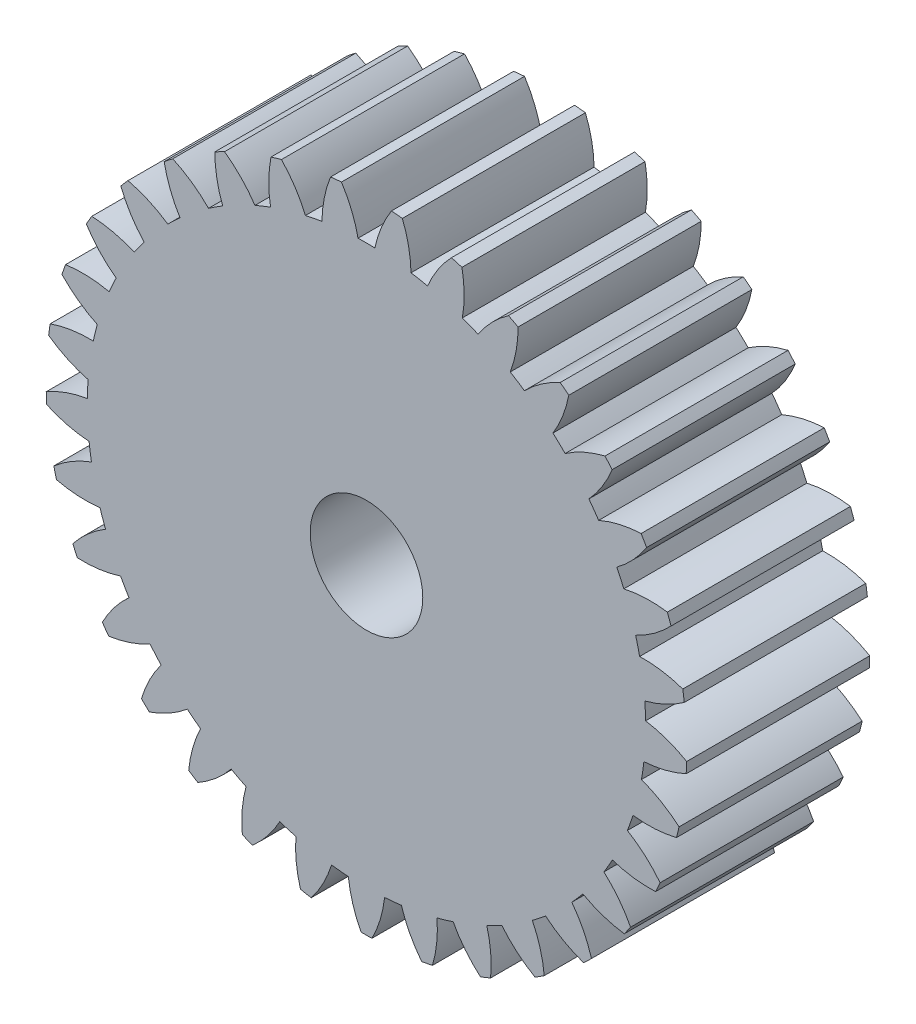
SolidWorks part; units mm, degrees
ref_plane "Alzado" through (0, 0, 0) normal (0, 0, 1) x (1, 0, 0)
ref_plane "Planta" through (0, 0, 0) normal (0, 1, 0) x (1, 0, 0)
ref_plane "Vista lateral" through (0, 0, 0) normal (1, 0, 0) x (0, 0, -1)
sketch "Croquis1" plane through (0, 0, 0) normal (0, 0, 1) x (1, 0, 0)
  line L0 (13.6206, 0) -> (-13.971, 0) construction
  line L1 (-0.46, 15.2421) -> (0, 0) construction
  line L2 (0.46, 15.2421) -> (0, 0) construction
  line L3 (1.3662, 17.4466) -> (0, 0) construction
  line L4 (1.9603, 17.3899) -> (0, 0) construction
  line L5 (0, -3.6901) -> (0, 21.5552) construction
  circle A0 centre (0, 0) radius 3.075
  arc A29 (2.4329, 15.0537) -> (1.9603, 17.3899) centre (-4.1661, 14.9347) ccw
  arc A30 (1.9603, 17.3899) -> (1.3662, 17.4466) centre (0, 0) ccw
  arc A31 (1.3662, 17.4466) -> (0.46, 15.2421) centre (6.9172, 13.8764) ccw
  arc A32 (0.46, 15.2421) -> (-0.46, 15.2421) centre (0, 0) ccw
  circle A133 centre (0, 0) radius 15.249 construction
  circle A134 centre (0, 0) radius 17.5 construction
  arc A135 (3.3363, 14.8796) -> (2.4329, 15.0537) centre (0, 0) ccw
  arc A136 (4.6433, 16.8728) -> (3.3363, 14.8796) centre (9.4183, 12.3166) ccw
  arc A137 (5.2159, 16.7046) -> (4.6433, 16.8728) centre (0, 0) ccw
  arc A138 (5.2378, 14.3212) -> (5.2159, 16.7046) centre (-1.2644, 15.4533) ccw
  arc A139 (6.092, 13.9793) -> (5.2378, 14.3212) centre (0, 0) ccw
  arc A140 (7.7526, 15.6891) -> (6.092, 13.9793) centre (11.5791, 10.3116) ccw
  arc A141 (8.283, 15.4156) -> (7.7526, 15.6891) centre (0, 0) ccw
  arc A142 (7.8535, 13.0712) -> (8.283, 15.4156) centre (1.683, 15.4133) ccw
  arc A143 (8.6275, 12.5737) -> (7.8535, 13.0712) centre (0, 0) ccw
  arc A144 (10.5816, 13.9384) -> (8.6275, 12.5737) centre (13.3213, 7.9339) ccw
  arc A145 (11.0508, 13.5695) -> (10.5816, 13.9384) centre (0, 0) ccw
  arc A146 (10.1853, 11.3487) -> (11.0508, 13.5695) centre (4.5696, 14.8163) ccw
  arc A147 (10.8512, 10.7137) -> (10.1853, 11.3487) centre (0, 0) ccw
  arc A148 (13.0283, 11.6839) -> (10.8512, 10.7137) centre (14.582, 5.2694) ccw
  arc A149 (13.4191, 11.2329) -> (13.0283, 11.6839) centre (0, 0) ccw
  arc A150 (12.149, 9.216) -> (13.4191, 11.2329) centre (7.291, 13.6837) ccw
  arc A151 (12.6827, 8.4665) -> (12.149, 9.216) centre (0, 0) ccw
  arc A152 (15.004, 9.0072) -> (12.6827, 8.4665) centre (15.3158, 2.4145) ccw
  arc A153 (15.3024, 8.4903) -> (15.004, 9.0072) centre (0, 0) ccw
  arc A154 (13.6736, 6.7502) -> (15.3024, 8.4903) centre (9.7489, 12.0566) ccw
  arc A155 (14.0558, 5.9133) -> (13.6736, 6.7502) centre (0, 0) ccw
  arc A156 (16.4375, 6.0049) -> (14.0558, 5.9133) centre (15.4959, -0.5276) ccw
  arc A157 (16.6327, 5.4409) -> (16.4375, 6.0049) centre (0, 0) ccw
  arc A158 (14.704, 4.0405) -> (16.6327, 5.4409) centre (11.8545, 9.9937) ccw
  arc A159 (14.9209, 3.1464) -> (14.704, 4.0405) centre (0, 0) ccw
  arc A160 (17.2769, 2.7855) -> (14.9209, 3.1464) centre (15.1161, -3.4507) ccw
  arc A161 (17.3618, 2.1948) -> (17.2769, 2.7855) centre (0, 0) ccw
  arc A162 (15.2029, 1.1848) -> (17.3618, 2.1948) centre (13.5316, 7.5696) ccw
  arc A163 (15.2467, 0.2657) -> (15.2029, 1.1848) centre (0, 0) ccw
  arc A164 (17.4918, -0.5345) -> (15.2467, 0.2657) centre (14.1898, -6.2491) ccw
  arc A165 (17.4634, -1.1306) -> (17.4918, -0.5345) centre (0, 0) ccw
  arc A166 (15.1524, -1.7138) -> (17.4634, -1.1306) centre (14.7196, 4.872) ccw
  arc A167 (15.0214, -2.6245) -> (15.1524, -1.7138) centre (0, 0) ccw
  arc A168 (17.0746, -3.8352) -> (15.0214, -2.6245) centre (12.7508, -8.8216) ccw
  arc A169 (16.9339, -4.4152) -> (17.0746, -3.8352) centre (0, 0) ccw
  arc A170 (14.5542, -4.5505) -> (16.9339, -4.4152) centre (15.3756, 1.9982) ccw
  arc A171 (14.2533, -5.4199) -> (14.5542, -4.5505) centre (0, 0) ccw
  arc A172 (16.0402, -6.9973) -> (14.2533, -5.4199) centre (10.8508, -11.0753) ccw
  arc A173 (15.7923, -7.5401) -> (16.0402, -6.9973) centre (0, 0) ccw
  arc A174 (13.43, -7.2226) -> (15.7923, -7.5401) centre (15.4759, -0.9477) ccw
  arc A175 (12.97, -8.0194) -> (13.43, -7.2226) centre (0, 0) ccw
  arc A176 (14.4261, -9.9064) -> (12.97, -8.0194) centre (8.5587, -12.9287) ccw
  arc A177 (14.0799, -10.3926) -> (14.4261, -9.9064) centre (0, 0) ccw
  arc A178 (11.8204, -9.6338) -> (14.0799, -10.3926) centre (15.0169, -3.8594) ccw
  arc A179 (11.2179, -10.3291) -> (11.8204, -9.6338) centre (0, 0) ccw
  arc A180 (12.2906, -12.4576) -> (11.2179, -10.3291) centre (5.9573, -14.3148) ccw
  arc A181 (11.8587, -12.8694) -> (12.2906, -12.4576) centre (0, 0) ccw
  arc A182 (9.7836, -11.6967) -> (11.8587, -12.8694) centre (14.0151, -6.6317) ccw
  arc A183 (9.0604, -12.2654) -> (9.7836, -11.6967) centre (0, 0) ccw
  arc A184 (9.7109, -14.5585) -> (9.0604, -12.2654) centre (3.1405, -15.1835) ccw
  arc A185 (9.2088, -14.8811) -> (9.7109, -14.5585) centre (0, 0) ccw
  arc A186 (7.3932, -13.3369) -> (9.2088, -14.8811) centre (12.5068, -9.1642) ccw
  arc A187 (6.5754, -13.7585) -> (7.3932, -13.3369) centre (0, 0) ccw
  arc A188 (6.7802, -16.1332) -> (6.5754, -13.7585) centre (0.2103, -15.5035) ccw
  arc A189 (6.2261, -16.355) -> (6.7802, -16.1332) centre (0, 0) ccw
  arc A190 (4.7356, -14.495) -> (6.2261, -16.355) centre (10.5465, -11.3655) ccw
  arc A191 (3.8528, -14.7543) -> (4.7356, -14.495) centre (0, 0) ccw
  arc A192 (3.6044, -17.1248) -> (3.8528, -14.7543) centre (-2.7276, -15.2631) ccw
  arc A193 (3.0184, -17.2377) -> (3.6044, -17.1248) centre (0, 0) ccw
  arc A194 (1.9068, -15.1293) -> (3.0184, -17.2377) centre (8.2049, -13.1561) ccw
  arc A195 (0.9909, -15.2168) -> (1.9068, -15.1293) centre (0, 0) ccw
  arc A196 (0.2984, -17.4975) -> (0.9909, -15.2168) centre (-5.5668, -14.4711) ccw
  arc A197 (-0.2984, -17.4975) -> (0.2984, -17.4975) centre (0, 0) ccw
  arc A198 (-0.9909, -15.2168) -> (-0.2984, -17.4975) centre (5.5668, -14.4711) ccw
  arc A199 (-1.9068, -15.1293) -> (-0.9909, -15.2168) centre (0, 0) ccw
  arc A200 (-3.0184, -17.2377) -> (-1.9068, -15.1293) centre (-8.2049, -13.1561) ccw
  arc A201 (-3.6044, -17.1248) -> (-3.0184, -17.2377) centre (0, 0) ccw
  arc A202 (-3.8528, -14.7543) -> (-3.6044, -17.1248) centre (2.7276, -15.2631) ccw
  arc A203 (-4.7356, -14.495) -> (-3.8528, -14.7543) centre (0, 0) ccw
  arc A204 (-6.2261, -16.355) -> (-4.7356, -14.495) centre (-10.5465, -11.3655) ccw
  arc A205 (-6.7802, -16.1332) -> (-6.2261, -16.355) centre (0, 0) ccw
  arc A206 (-6.5754, -13.7585) -> (-6.7802, -16.1332) centre (-0.2103, -15.5035) ccw
  arc A207 (-7.3932, -13.3369) -> (-6.5754, -13.7585) centre (0, 0) ccw
  arc A208 (-9.2088, -14.8811) -> (-7.3932, -13.3369) centre (-12.5068, -9.1642) ccw
  arc A209 (-9.7109, -14.5585) -> (-9.2088, -14.8811) centre (0, 0) ccw
  arc A210 (-9.0604, -12.2654) -> (-9.7109, -14.5585) centre (-3.1405, -15.1835) ccw
  arc A211 (-9.7836, -11.6967) -> (-9.0604, -12.2654) centre (0, 0) ccw
  arc A212 (-11.8587, -12.8694) -> (-9.7836, -11.6967) centre (-14.0151, -6.6317) ccw
  arc A213 (-12.2906, -12.4576) -> (-11.8587, -12.8694) centre (0, 0) ccw
  arc A214 (-11.2179, -10.3291) -> (-12.2906, -12.4576) centre (-5.9573, -14.3148) ccw
  arc A215 (-11.8204, -9.6338) -> (-11.2179, -10.3291) centre (0, 0) ccw
  arc A216 (-14.0799, -10.3926) -> (-11.8204, -9.6338) centre (-15.0169, -3.8594) ccw
  arc A217 (-14.4261, -9.9064) -> (-14.0799, -10.3926) centre (0, 0) ccw
  arc A218 (-12.97, -8.0194) -> (-14.4261, -9.9064) centre (-8.5587, -12.9287) ccw
  arc A219 (-13.43, -7.2226) -> (-12.97, -8.0194) centre (0, 0) ccw
  arc A220 (-15.7923, -7.5401) -> (-13.43, -7.2226) centre (-15.4759, -0.9477) ccw
  arc A221 (-16.0402, -6.9973) -> (-15.7923, -7.5401) centre (0, 0) ccw
  arc A222 (-14.2533, -5.4199) -> (-16.0402, -6.9973) centre (-10.8508, -11.0753) ccw
  arc A223 (-14.5542, -4.5505) -> (-14.2533, -5.4199) centre (0, 0) ccw
  arc A224 (-16.9339, -4.4152) -> (-14.5542, -4.5505) centre (-15.3756, 1.9982) ccw
  arc A225 (-17.0746, -3.8352) -> (-16.9339, -4.4152) centre (0, 0) ccw
  arc A226 (-15.0214, -2.6245) -> (-17.0746, -3.8352) centre (-12.7508, -8.8216) ccw
  arc A227 (-15.1524, -1.7138) -> (-15.0214, -2.6245) centre (0, 0) ccw
  arc A228 (-17.4634, -1.1306) -> (-15.1524, -1.7138) centre (-14.7196, 4.872) ccw
  arc A229 (-17.4918, -0.5345) -> (-17.4634, -1.1306) centre (0, 0) ccw
  arc A230 (-15.2467, 0.2657) -> (-17.4918, -0.5345) centre (-14.1898, -6.2491) ccw
  arc A231 (-15.2029, 1.1848) -> (-15.2467, 0.2657) centre (0, 0) ccw
  arc A232 (-17.3618, 2.1948) -> (-15.2029, 1.1848) centre (-13.5316, 7.5696) ccw
  arc A233 (-17.2769, 2.7855) -> (-17.3618, 2.1948) centre (0, 0) ccw
  arc A234 (-14.9209, 3.1464) -> (-17.2769, 2.7855) centre (-15.1161, -3.4507) ccw
  arc A235 (-14.704, 4.0405) -> (-14.9209, 3.1464) centre (0, 0) ccw
  arc A236 (-16.6327, 5.4409) -> (-14.704, 4.0405) centre (-11.8545, 9.9937) ccw
  arc A237 (-16.4375, 6.0049) -> (-16.6327, 5.4409) centre (0, 0) ccw
  arc A238 (-14.0558, 5.9133) -> (-16.4375, 6.0049) centre (-15.4959, -0.5276) ccw
  arc A239 (-13.6736, 6.7502) -> (-14.0558, 5.9133) centre (0, 0) ccw
  arc A240 (-15.3024, 8.4903) -> (-13.6736, 6.7502) centre (-9.7489, 12.0566) ccw
  arc A241 (-15.004, 9.0072) -> (-15.3024, 8.4903) centre (0, 0) ccw
  arc A242 (-12.6827, 8.4665) -> (-15.004, 9.0072) centre (-15.3158, 2.4145) ccw
  arc A243 (-12.149, 9.216) -> (-12.6827, 8.4665) centre (0, 0) ccw
  arc A244 (-13.4191, 11.2329) -> (-12.149, 9.216) centre (-7.291, 13.6837) ccw
  arc A245 (-13.0283, 11.6839) -> (-13.4191, 11.2329) centre (0, 0) ccw
  arc A246 (-10.8512, 10.7137) -> (-13.0283, 11.6839) centre (-14.582, 5.2694) ccw
  arc A247 (-10.1853, 11.3487) -> (-10.8512, 10.7137) centre (0, 0) ccw
  arc A248 (-11.0508, 13.5695) -> (-10.1853, 11.3487) centre (-4.5696, 14.8163) ccw
  arc A249 (-10.5816, 13.9384) -> (-11.0508, 13.5695) centre (0, 0) ccw
  arc A250 (-8.6275, 12.5737) -> (-10.5816, 13.9384) centre (-13.3213, 7.9339) ccw
  arc A251 (-7.8535, 13.0712) -> (-8.6275, 12.5737) centre (0, 0) ccw
  arc A252 (-8.283, 15.4156) -> (-7.8535, 13.0712) centre (-1.683, 15.4133) ccw
  arc A253 (-7.7526, 15.6891) -> (-8.283, 15.4156) centre (0, 0) ccw
  arc A254 (-6.092, 13.9793) -> (-7.7526, 15.6891) centre (-11.5791, 10.3116) ccw
  arc A255 (-5.2378, 14.3212) -> (-6.092, 13.9793) centre (0, 0) ccw
  arc A256 (-5.2159, 16.7046) -> (-5.2378, 14.3212) centre (1.2644, 15.4533) ccw
  arc A257 (-4.6433, 16.8728) -> (-5.2159, 16.7046) centre (0, 0) ccw
  arc A258 (-3.3363, 14.8796) -> (-4.6433, 16.8728) centre (-9.4183, 12.3166) ccw
  arc A259 (-2.4329, 15.0537) -> (-3.3363, 14.8796) centre (0, 0) ccw
  arc A260 (-1.9603, 17.3899) -> (-2.4329, 15.0537) centre (4.1661, 14.9347) ccw
  arc A261 (-1.3662, 17.4466) -> (-1.9603, 17.3899) centre (0, 0) ccw
  arc A262 (-0.46, 15.2421) -> (-1.3662, 17.4466) centre (-6.9172, 13.8764) ccw
  point P244 (0, 0)
  dimension "D1" = 6.15
  dimension "D2" = 88.271
  dimension "D3" = 35
  dimension "D8" = 6.9172
  dimension "D11" = 30.498
  dimension "D4" = 91.729
  dimension "D5" = 94.477
  dimension "D6" = 96.432
  dimension "D7" = 13.8764
  dimension "D9" = 4.1661
  dimension "D10" = 14.9347
  dimension "D12" = 33
extrude "Saliente-Extruir1" add sketch "Croquis1" along normal blind 10
